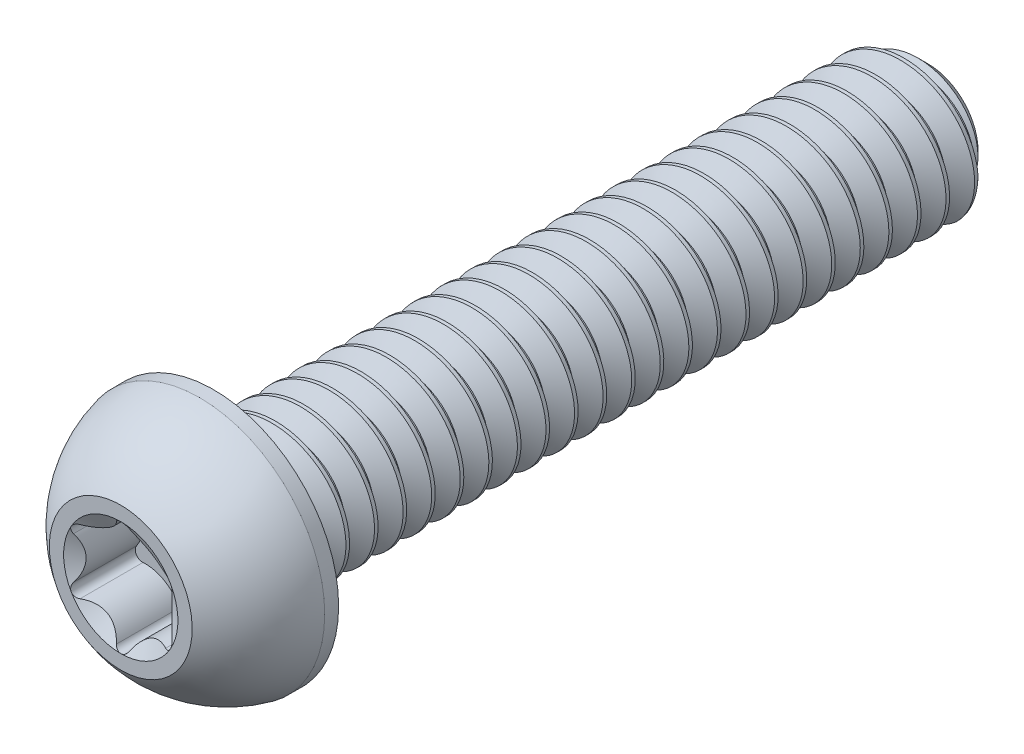
SolidWorks part; units mm, degrees
ref_plane "Front" through (0, 0, 0) normal (0, 0, 1) x (1, 0, 0)
ref_plane "Top" through (0, 0, 0) normal (0, 1, 0) x (1, 0, 0)
ref_plane "Right" through (0, 0, 0) normal (1, 0, 0) x (0, 0, -1)
sketch "Sketch1" plane through (0, 0, 0) normal (1, 0, 0) x (0, 0, -1)
  line L2 (1.3, 1) -> (11.3, 1)
  line L3 (11.3, 1) -> (11.3, 0)
  line L4 (11.3, 0) -> (1.3, 0)
  line L6 (1.105, 1.75) -> (1.3, 1.75) construction
  line L7 (11.3, 1) -> (11.3, -1) construction
  line L8 (0, 0) -> (1.3, 0) construction
  line L9 (1.3, 1.75) -> (1.3, -1.75) construction
  line L11 (1.3, 1) -> (1.3, 0)
  line L14 (0, 0) -> (0, 1) construction
  arc A3 (0, 1) -> (1.105, 1.75) centre (1.4858, 0) cw construction
  dimension "D1" = 0.195
  dimension "Head Ht" = 1.3
  dimension "Head Dia" = 3.5
  dimension "Dia" = 2
  dimension "Lg" = 10
revolve "Revolve1" add sketch "Sketch1" angle 360 mid plane about L4
sketch "Sketch3" plane through (0, 0, -11.3) normal (0, 0, -1) x (-1, 0, 0)
  circle A0 centre (0, 0) radius 1
curve "Helix/Spiral1" pitch 0.4 height 10.4 radius 1 centre (0, 0, -11.3) axis (0, 0, 1) start towards (0, 1, 0)
sketch "Sketch2" plane through (0, 0, 0) normal (1, 0, 0) x (0, 0, -1)
  line L0 (11.3, 1) -> (11.65, 1)
  line L1 (11.65, 1) -> (11.5, 0.7402)
  line L2 (11.5, 0.7402) -> (11.45, 0.7402)
  line L3 (11.45, 0.7402) -> (11.3, 1)
  line L4 (11.375, 0.8701) -> (11.575, 0.8701) construction
  dimension "D1" = 60
  dimension "D2" = 0.05
  dimension "D3" = 0.2
chamfer "Chamfer1" distance 0.3 angle 45 1 edges at (0, 1, -11.3)
sweep "Cut-Sweep1" cut profiles "Sketch2" path "Helix/Spiral1"
sketch "Sketch7" plane through (0, 0, 0) normal (1, 0, 0) x (0, 0, -1)
  line L0 (0, 0) -> (0, 1) construction
  line L6 (1.105, 1.75) -> (1.3, 1.75) construction
  line L8 (0, 0) -> (1.3, 0) construction
  line L11 (1.3, 1.75) -> (1.3, -1.75) construction
  line L12 (1.105, 1.75) -> (1.3, 1.75)
  line L13 (0, 0) -> (1.3, 0)
  line L15 (1.3, 1.75) -> (1.3, 0)
  line L16 (0, 1) -> (0, 0)
  arc A2 (1.105, 1.75) -> (0, 1) centre (1.4858, 0) ccw construction
  arc A3 (1.105, 1.75) -> (0, 1) centre (1.4858, 0) ccw
revolve "Revolve2" add sketch "Sketch7" angle 360 mid plane about L13
sketch "Sketch11" plane through (0, 0, 0) normal (0, 0, 1) x (1, 0, 0)
  line L0 (0, 0) -> (-0.6928, 0.4)
  line L1 (0, 0) -> (-0.6928, -0.4)
  line L2 (0, 0.8) -> (0, 0.7) construction
  line L3 (0, 0.7) -> (0, 0.6) construction
  line L4 (4.18, 0) -> (-4.18, 0) construction
  circle A0 centre (0, 0) radius 0.6 construction
  circle A1 centre (0, 0) radius 0.7 construction
  circle A2 centre (0, 0) radius 0.8 construction
  arc A3 (-0.6894, 0.2944) -> (-0.6894, -0.2944) centre (-1.1298, 0) cw
  arc A4 (-0.6894, 0.2944) -> (-0.6928, 0.4) centre (-0.6062, 0.35) cw
  arc A5 (-0.6894, -0.2944) -> (-0.6928, -0.4) centre (-0.6062, -0.35) ccw
  dimension "D1" = 1.2
  dimension "D2" = 1.6
  dimension "D3" = 30
extrude "Cut-Extrude4" cut sketch "Sketch11" against normal blind 0.91
pattern_circular "CirPattern1" count 6 over 360 of "Cut-Extrude4"
sketch "Sketch6" plane through (0, 0, 0) normal (0, 0, 1) x (1, 0, 0)
  circle A0 centre (0, 0) radius 0.8 construction
  circle A1 centre (0, 0) radius 0.8
extrude "Cut-Extrude3" cut sketch "Sketch6" against normal blind 0.91 draft 60
sketch "Sketch9" [suppressed] plane through (0, 0, -5.5) normal (0, 0, 1) x (1, 0, 0)
  circle A2 centre (0, 0) radius 5
extrude "Boss-Extrude2" [suppressed] add sketch "Sketch9" against normal offset from surface (13 mm away) 32 up to face at (0, 0.7, -11.3)
sketch "Sketch10" plane through (0, 0, 0) normal (1, 0, 0) x (0, 0, -1)
  line L0 (11.3, 1) -> (11.3, -1) construction
  point P0 (10.7, -1)
  dimension "D1" = 0.6
equation "\"D3@Helix/Spiral1\" = \"Lg@Sketch1\" + \"D4@Helix/Spiral1\""
equation "\"D2@Sketch2\" = \"D4@Helix/Spiral1\" * .125"
equation "\"D3@Sketch2\" = \"D4@Helix/Spiral1\" * .5"
equation "\"D1@Chamfer1\" = \"D4@Helix/Spiral1\" * .75"
equation "\"D1@Sketch1\" = \"Head Ht@Sketch1\" * .15"
equation "\"D1@Sketch10\" = \"D4@Helix/Spiral1\" * 1.5"
equation "\"D2@Sketch11\" = \"Dia@Sketch1\" * .8"
equation "\"D1@Sketch11\" = \"D2@Sketch11\" * .75"
equation "\"D1@Cut-Extrude4\" = \"Head Ht@Sketch1\" * .7"
equation "\"D1@Cut-Extrude3\" = \"D1@Cut-Extrude4\""
